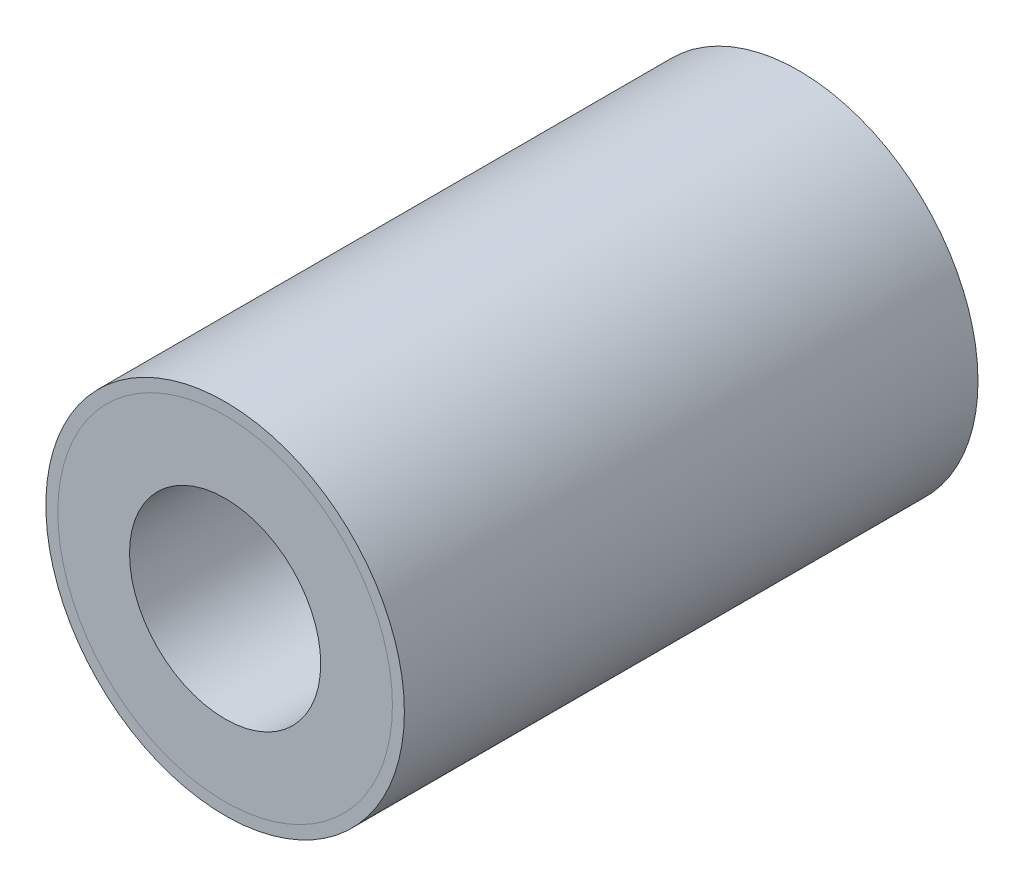
SolidWorks part; units mm, degrees
material "Acier inoxydable chromé"
ref_plane "Front Plane" through (0, 0, 0) normal (0, 0, 1) x (1, 0, 0)
ref_plane "Top Plane" through (0, 0, 0) normal (0, 1, 0) x (1, 0, 0)
ref_plane "Right Plane" through (0, 0, 0) normal (1, 0, 0) x (0, 0, -1)
sketch "Sketch1" plane through (0, 0, 0) normal (0, 0, 1) x (1, 0, 0)
  circle A0 centre (0, 0) radius 4
  circle A1 centre (0, 0) radius 7
  circle A2 centre (0, 0) radius 7.5
  dimension "D1" = 8
  dimension "D2" = 14
  dimension "D3" = 15
extrude "Boss-Extrude1" add sketch "Sketch1" along normal blind 24 contours A1 A0 region at (-6.802, 0, 0)
extrude "Boss-Extrude2" add sketch "Sketch1<3>" along normal blind 24 separate body contours A2 A1 region at (-7.2879, 0, 0)
sketch "Sketch1<3>" plane through (0, 0, 0) normal (0, 0, 1) x (1, 0, 0) same geometry as "Sketch1"
